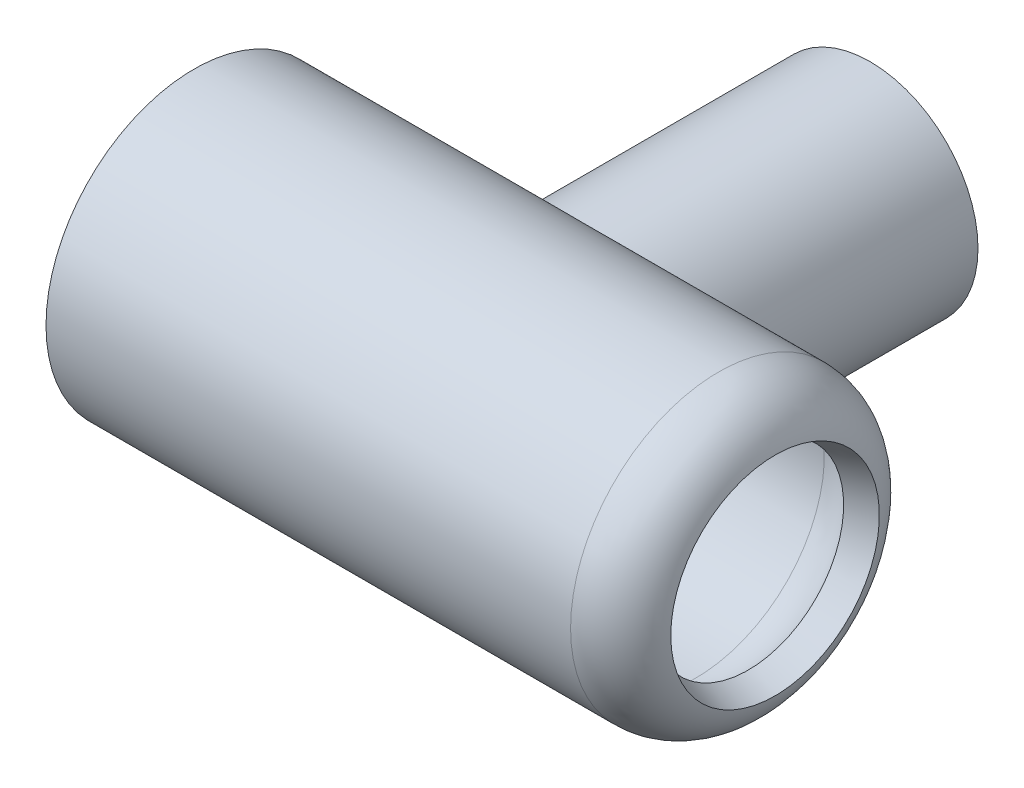
SolidWorks part; units mm, degrees
ref_plane "Vorne" through (0, 0, 0) normal (0, 0, 1) x (1, 0, 0)
ref_plane "Oben" through (0, 0, 0) normal (0, 1, 0) x (1, 0, 0)
ref_plane "Rechts" through (0, 0, 0) normal (1, 0, 0) x (0, 0, -1)
sketch "Skizze1" plane through (0, 0, 0) normal (0, 0, 1) x (1, 0, 0)
  line L0 (-16.3509, 0) -> (16.3509, 0) construction
  line L1 (-25, 12.7) -> (20, 12.7)
  line L2 (25, 7.7) -> (25, 0)
  line L3 (18.0198, 11.05) -> (-25, 11.05)
  line L4 (-25, 11.05) -> (-25, 12.7)
  line L5 (0, 0) -> (0, 5.5321) construction
  line L6 (23.0198, 6.05) -> (23.0198, 0)
  line L7 (23.0198, 0) -> (25, 0)
  arc A0 (20, 12.7) -> (25, 7.7) centre (20, 7.7) cw
  arc A1 (23.0198, 6.05) -> (18.0198, 11.05) centre (18.0198, 6.05) ccw
  point P13 (25, 12.7)
  dimension "D5" = 5
  dimension "D1" = 25.4
  dimension "D2" = 1.65
  dimension "D3" = 50
  dimension "D4" = 1.9802
revolve "Rotation1" add sketch "Skizze1" angle 360 about L0
sketch "Skizze2" plane through (0, 0, 0) normal (0, 1, 0) x (1, 0, 0)
  line L0 (-29.5239, 0) -> (29.5239, 0) construction
  line L1 (22, 0) -> (22, 8)
  line L2 (22, 8) -> (25, 9)
  line L3 (25, 9) -> (25, 0)
  line L4 (25, 0) -> (22, 0)
  line L5 (25, -7.7) -> (25, 7.7) construction
  point P9 (22, 8)
  dimension "D1" = 16
  dimension "D2" = 3
  dimension "D3" = 9
revolve "Schnitt-Rotation1" cut sketch "Skizze2" angle 360 about L0
sketch "Skizze3" plane through (0, 0, 0) normal (0, 0, 1) x (1, 0, 0)
  circle A0 centre (0, 0) radius 9.25
  dimension "D1" = 18.5
extrude "Schnitt-Linear austragen1" cut sketch "Skizze3" against normal blind 30
ref_plane "Ebene1" through (0, 0, -8) normal (0, 0, 1) x (1, 0, 0)
sketch "Skizze5" plane through (0, 0, -8) normal (0, 0, 1) x (1, 0, 0)
  circle A0 centre (0, 0) radius 9.25
  circle A1 centre (0, 0) radius 5.72
  dimension "D1" = 18.5
  dimension "D2" = 11.44
extrude "Aufsatz-Linear austragen1" add sketch "Skizze5" against normal blind 25
other "APunkt2" parameters "Durchmesser"=12.7, "Stumpflänge"=0
ref_axis "Achse2" through (-35, 0, 0) along (1, 0, 0)
other "LPunkt1"
